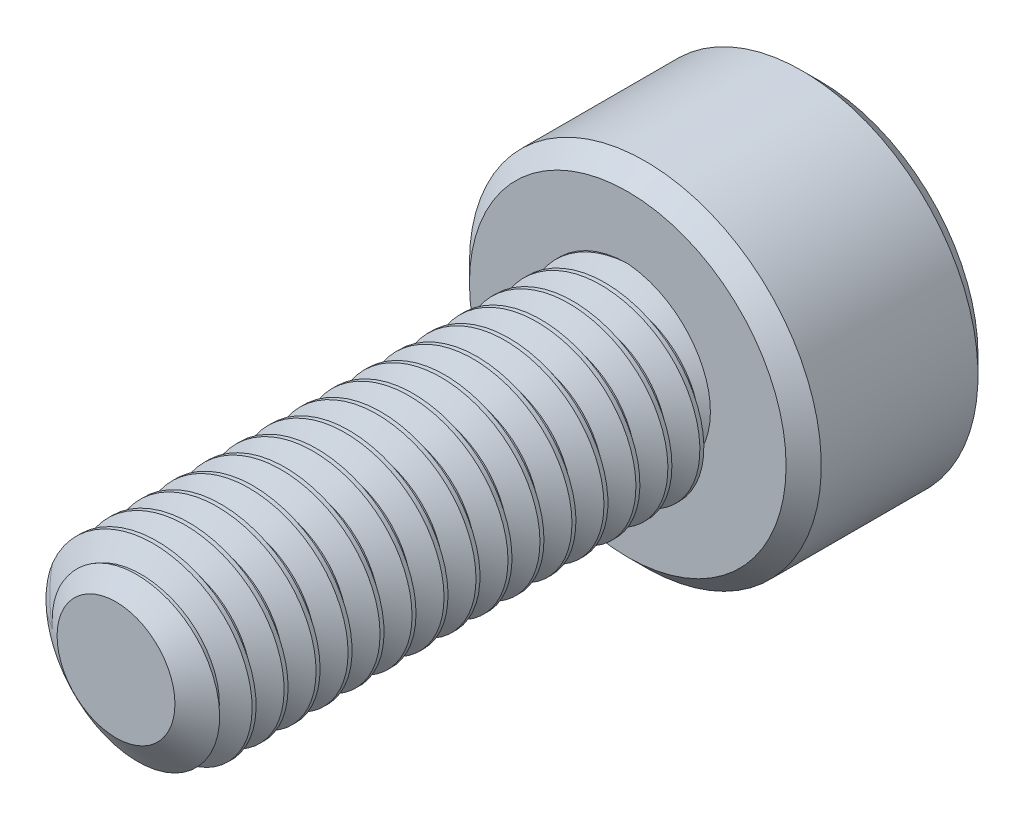
SolidWorks part; units mm, degrees
other "DetailItem1"
ref_plane "Front Plane" through (0, 0, 0) normal (0, 0, 1) x (1, 0, 0)
ref_plane "Top Plane" through (0, 0, 0) normal (0, 1, 0) x (1, 0, 0)
ref_plane "Right Plane" through (0, 0, 0) normal (1, 0, 0) x (0, 0, -1)
sketch "Sketch1" plane through (0, 0, 0) normal (0, 0, 1) x (1, 0, 0)
  circle A0 centre (0, 0) radius 1.5
  dimension "OD" = 3
extrude "Extrude1" add sketch "Sketch1" against normal blind 8
sketch "Sketch2" plane through (0, 0, 0) normal (0, 0, 1) x (1, 0, 0)
  circle A0 centre (0, 0) radius 1.5 construction
  circle A1 centre (0, 0) radius 1.5
curve "Helix/Spiral1" pitch 0.5 height 8.5 radius 1.5 centre (0, 0, 0) axis (0, 0, -1) start towards (0, 1, 0) parameters "pitch"=0.5
sketch "Sketch3" plane through (0, 0, 0) normal (1, 0, 0) x (0, 0, -1)
  line L0 (-0.4375, 1.5) -> (-0.25, 1.1752)
  line L1 (-0.25, 1.1752) -> (-0.1875, 1.1752)
  line L2 (-0.1875, 1.1752) -> (0, 1.5)
  line L3 (-0.4375, 1.5) -> (0, 1.5)
  line L4 (-0.2187, 1.5) -> (-0.2188, 1.1752) construction
  line L5 (-0.3438, 1.3376) -> (-0.0938, 1.3376) construction
  line L6 (0, 1.5) -> (0, -1.5) construction
  dimension "D1" = 0.0625
  dimension "D2" = 0.25
  dimension "D3" = 60
sweep "Cut-Sweep1" cut profiles "Sketch3" path "Helix/Spiral1" align with end faces yes
sketch "Sketch4" plane through (0, 0, 0) normal (1, 0, 0) x (0, 0, -1)
  line L0 (0.4053, 1.5) -> (0, 0.9212)
  line L1 (0, 0.9212) -> (0, 1.5)
  line L2 (0.4053, 1.5) -> (0, 1.5)
  line L3 (-0.4375, 1.5) -> (0, 1.5) construction
  line L4 (0, 0) -> (7.0209, 0) construction
  dimension "D1" = 55
  dimension "D2" = 0.254
revolve "Cut-Revolve1" cut sketch "Sketch4" angle 360 about L4
sketch "Sketch6" plane through (0, 0, -8) normal (0, 0, -1) x (-1, 0, 0)
  circle A0 centre (0, 0) radius 2.75
  dimension "head dia" = 5.5
extrude "Extrude2" add sketch "Sketch6" along normal blind 3
sketch "Sketch7" plane through (0, 0, -11) normal (0, 0, -1) x (-1, 0, 0)
  line L1 (0, 1.4434) -> (-1.25, 0.7217)
  line L2 (-1.25, 0.7217) -> (-1.25, -0.7217)
  line L3 (-1.25, -0.7217) -> (0, -1.4434)
  line L4 (0, -1.4434) -> (1.25, -0.7217)
  line L5 (1.25, -0.7217) -> (1.25, 0.7217)
  line L6 (1.25, 0.7217) -> (0, 1.4434)
  circle A0 centre (0, 0) radius 1.25 construction
  dimension "hex dia" = 2.5
extrude "Cut-Extrude1" cut sketch "Sketch7" against normal blind 1.875
sketch "Sketch8" plane through (0, 0, -11) normal (0, 0, -1) x (-1, 0, 0)
  circle A0 centre (0, 0) radius 1.4434
extrude "Cut-Extrude2" cut sketch "Sketch8" against normal through all draft 45
chamfer "Chamfer1" distance 0.275 angle 45 2 edges at (-2.75, 0, -11) (-2.75, 0, -8)
sketch "Sketch10" plane through (0, 0, -8) normal (0, 0, 1) x (1, 0, 0)
  circle A1 centre (0, 0) radius 1.5
  circle A2 centre (0, 0) radius 1.5
  dimension "D1" = 0
ref_plane "Plane1" through (0, 0, 0) normal (0, 0, 1) x (1, 0, 0)
extrude "partial thread" [suppressed] add sketch "Sketch10" along normal up to surface (4 mm away) separate body
chamfer "Chamfer2" [suppressed] distance 0.06 angle 45
combine bodies "Combine1" [suppressed] operation type add bodies to combine 107 108
sketch "Sketch9" plane through (0, 0, 0) normal (1, 0, 0) x (0, 0, -1)
  line L0 (0, 1.5) -> (0, -1.5) construction
  line L1 (1.25, 1.5) -> (1.25, -1.5) construction
  dimension "D1" = 1.25
equation "\"D3@Helix/Spiral1\" = \"screw length@Extrude1\"+\"pitch@Helix/Spiral1\""
equation "\"D1@Sketch3\" = \"pitch@Helix/Spiral1\"*.125"
equation "\"D2@Sketch3\" = \"pitch@Helix/Spiral1\"*.5"
equation "\"D1@Cut-Extrude1\" = \"hex dia@Sketch7\"*.75"
equation "\"D1@Chamfer1\" = \"head dia@Sketch6\"*.05"
equation "\"D1@Sketch9\" = \"pitch@Helix/Spiral1\"*2.5"
equation "\"D1@Chamfer2\"=\"OD@Sketch1\"*.02"
